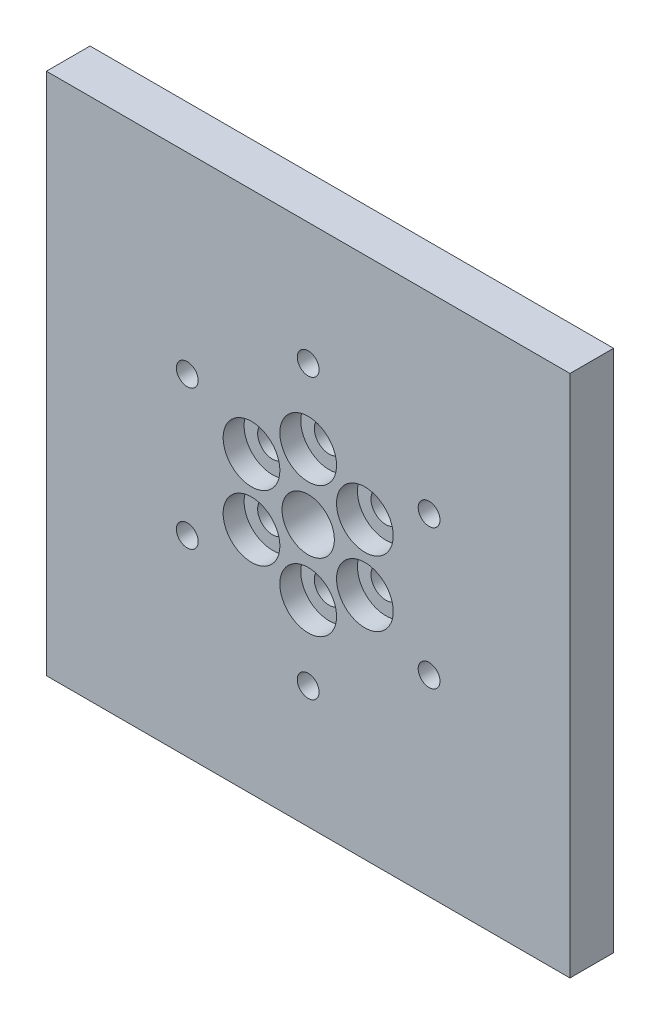
SolidWorks part; units mm, degrees
material "6061-T6 (SS)"
ref_plane "Front Plane" through (0, 0, 0) normal (0, 0, 1) x (1, 0, 0)
ref_plane "Top Plane" through (0, 0, 0) normal (0, 1, 0) x (1, 0, 0)
ref_plane "Right Plane" through (0, 0, 0) normal (1, 0, 0) x (0, 0, -1)
sketch "Sketch1" plane through (0, 0, 0) normal (0, 0, 1) x (1, 0, 0)
  line L1 (0, 0) -> (60, 0)
  line L2 (0, 0) -> (0, 60)
  line L3 (0, 60) -> (60, 60)
  line L4 (60, 0) -> (60, 60)
  dimension "D1" = 60
  dimension "D2" = 60
extrude "Boss-Extrude1" add sketch "Sketch1" along normal blind 5
sketch "Sketch2" plane through (0, 0, 5) normal (0, 0, 1) x (1, 0, 0)
  line L0 (0, 60) -> (60, 0) construction
  line L1 (60, 0) -> (60, 60) construction
  line L2 (60, 60) -> (0, 0) construction
  point P12 (30, 30)
hole_wizard "Ø6.0mm Dowel Hole1" positions "Sketch2" profile "Sketch3" hole size "Ø6.0" standard "DIN" end condition through all
sketch "Sketch3" plane through (30, 30, 5) normal (1, 0, 0) x (0, -1, 0)
  line L0 (0, 0) -> (0, 5)
  line L1 (0, 5) -> (3, 5)
  line L2 (3, 5) -> (3, 0)
  line L5 (3, 0) -> (0, 0)
  line L11 (0, -6.35) -> (0, 107.95) construction
  dimension "Thru Hole Dia." = 6
  dimension "Thru Hole Depth" = 5
sketch "Sketch10" plane through (0, 0, 5) normal (0, 0, 1) x (1, 0, 0)
  circle A0 centre (30, 30) radius 7.5
  point P5 (30, 37.5)
  point P12 (36.4952, 33.75)
  point P13 (36.4952, 26.25)
  point P14 (30, 22.5)
  point P15 (23.5048, 26.25)
  point P16 (23.5048, 33.75)
  dimension "D1" = 15
  dimension "D2" = 6
hole_wizard "CBORE for M3 Hex Socket Thin Head Cap Screw4" positions "Sketch10" profile "Sketch11" counterbore size "M3" standard "DIN" end condition through all
sketch "Sketch11" plane through (23.5048, 33.75, 5) normal (1, 0, 0) x (0, -1, 0)
  line L0 (0, 0) -> (0, 5)
  line L1 (0, 5) -> (1.7, 5)
  line L3 (1.7, 5) -> (1.7, 2.4)
  line L4 (1.7, 2.4) -> (3.25, 2.4)
  line L5 (3.25, 2.4) -> (3.25, 0)
  line L7 (3.25, 0) -> (0, 0)
  line L11 (0, -6.35) -> (0, 107.95) construction
  dimension "Thru Hole Dia." = 3.4
  dimension "Thru Hole Depth" = 5
  dimension "C'Bore Dia." = 6.5
  dimension "C'Bore Depth" = 2.4
sketch "Sketch12" plane through (0, 0, 5) normal (0, 0, 1) x (1, 0, 0)
  circle A0 centre (30, 30) radius 16
  point P4 (30, 46)
  point P11 (43.8564, 38)
  point P12 (43.8564, 22)
  point P13 (30, 14)
  point P14 (16.1436, 22)
  point P15 (16.1436, 38)
  dimension "D1" = 32
  dimension "D2" = 6
hole_wizard "Tap Drill for M3 Tap1" positions "Sketch12" profile "Sketch13" hole size "M3" standard "DIN" end condition through all
sketch "Sketch13" plane through (16.1436, 38, 5) normal (1, 0, 0) x (0, -1, 0)
  line L0 (0, 0) -> (0, 5)
  line L1 (0, 5) -> (1.25, 5)
  line L2 (1.25, 5) -> (1.25, 0)
  line L5 (1.25, 0) -> (0, 0)
  line L11 (0, -6.35) -> (0, 107.95) construction
  dimension "Thru Hole Dia." = 2.5
  dimension "Thru Hole Depth" = 5
